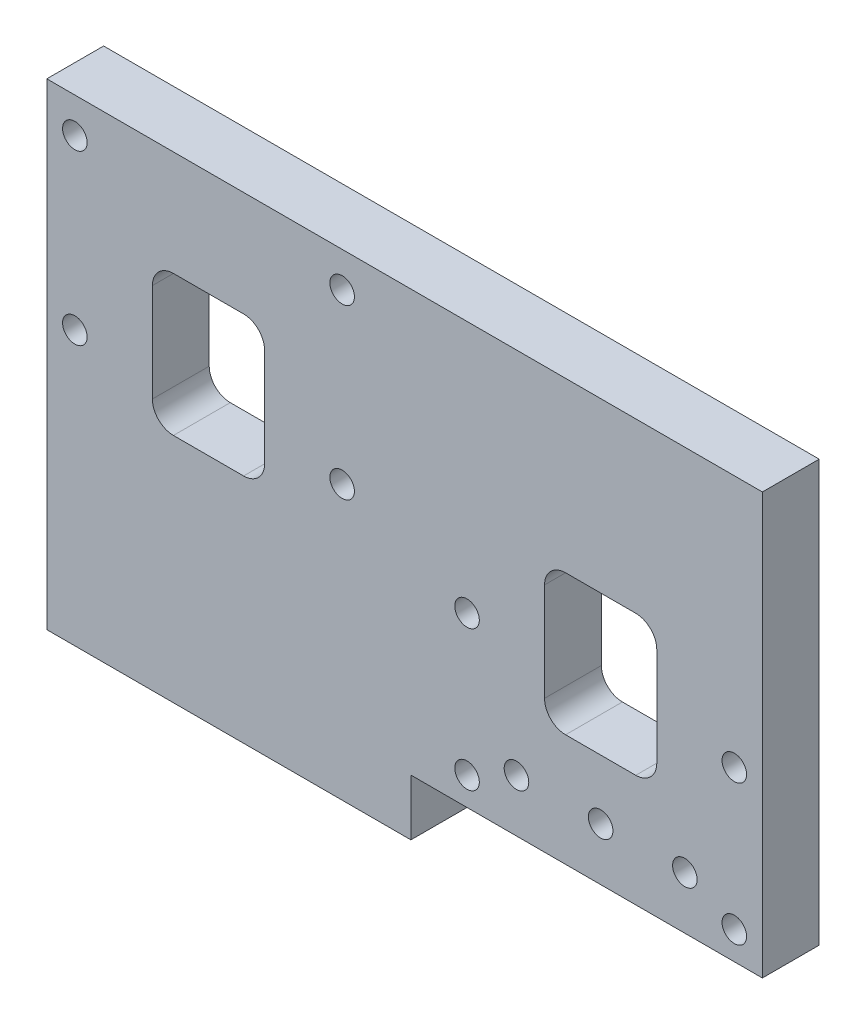
SolidWorks part; units mm, degrees
ref_plane "Plan de face" through (0, 0, 0) normal (0, 0, 1) x (1, 0, 0)
ref_plane "Plan de dessus" through (0, 0, 0) normal (0, 1, 0) x (1, 0, 0)
ref_plane "Plan de droite" through (0, 0, 0) normal (1, 0, 0) x (0, 0, -1)
sketch "Esquisse1" plane through (0, 0, 0) normal (0, 0, 1) x (1, 0, 0)
  line L1 (0, 0) -> (102, 0)
  line L2 (0, 0) -> (0, 60)
  line L3 (0, 60) -> (102, 60)
  line L4 (102, 0) -> (102, 60)
  dimension "D1" = 102
  dimension "D2" = 60
extrude "Boss.-Extru.1" add sketch "Esquisse1" along normal blind 8.1
sketch "Esquisse2" plane through (0, 0, 8.1) normal (0, 0, 1) x (1, 0, 0)
  line L0 (4, 31) -> (4, 55) construction
  line L1 (0, 60) -> (0, 0) construction
  line L2 (102, 60) -> (0, 60) construction
  line L3 (98, 4) -> (98, 24) construction
  line L4 (0, 0) -> (102, 0) construction
  line L5 (102, 0) -> (102, 60) construction
  line L6 (78.95, 0) -> (78.95, 26.94) construction
  line L7 (59.9, 4) -> (59.9, 24) construction
  line L8 (23.05, 60) -> (23.05, 33.0789) construction
  line L9 (42.1, 31) -> (42.1, 55) construction
  line L10 (78.95, 7.5) -> (66.95, 7.5) construction
  circle A0 centre (4, 55) radius 1.75
  circle A1 centre (4, 31) radius 1.75
  circle A2 centre (98, 24) radius 1.75
  circle A3 centre (98, 4) radius 1.75
  circle A4 centre (59.9, 4) radius 1.75
  circle A5 centre (59.9, 24) radius 1.75
  circle A6 centre (42.1, 31) radius 1.75
  circle A7 centre (42.1, 55) radius 1.75
  circle A8 centre (66.95, 7.5) radius 1.75
  circle A9 centre (78.95, 7.5) radius 1.75
  circle A10 centre (90.95, 7.5) radius 1.75
  dimension "D1" = 3.5
  dimension "D2" = 4
  dimension "D11" = 12
  dimension "D12" = 3.5
  dimension "D3" = 5
  dimension "D4" = 24
  dimension "D5" = 4
  dimension "D6" = 4
  dimension "D7" = 20
  dimension "D8" = 38.1
  dimension "D9" = 38.1
  dimension "D10" = 7.5
extrude "Enlèv. mat.-Extru.1" cut sketch "Esquisse2" against normal through all
sketch "Esquisse5" plane through (0, 0, 8.1) normal (0, 0, 1) x (1, 0, 0)
  line L0 (102, 0) -> (102, 60) construction
  line L1 (0, 0) -> (51.9, 0)
  line L2 (0, 0) -> (0, -8)
  line L3 (0, -8) -> (51.9, -8)
  line L4 (51.9, 0) -> (51.9, -8)
  dimension "D1" = 8
  dimension "D2" = 50.1
extrude "Boss.-Extru.2" add sketch "Esquisse5" against normal up to vertex (8.1 mm away) up to point (0, 0, 0)
sketch "Esquisse6" plane through (0, 0, 8.1) normal (0, 0, 1) x (1, 0, 0)
  line L0 (4, 55) -> (42.1, 55) construction
  line L1 (15.05, 45) -> (31.05, 45)
  line L2 (15.05, 45) -> (15.05, 25)
  line L3 (15.05, 25) -> (31.05, 25)
  line L4 (31.05, 45) -> (31.05, 25)
  line L5 (86.95, 36) -> (70.95, 36)
  line L6 (86.95, 36) -> (86.95, 16)
  line L7 (86.95, 16) -> (70.95, 16)
  line L8 (70.95, 36) -> (70.95, 16)
  line L9 (23.05, 45) -> (23.05, 55) construction
  line L10 (59.9, 24) -> (98, 24) construction
  line L11 (78.95, 16) -> (78.95, 24) construction
  line L12 (51.9, 0) -> (102, 0) construction
  point P22 (76.95, 0)
  dimension "D1" = 16
  dimension "D2" = 20
  dimension "D3" = 10
  dimension "D4" = 16
extrude "Enlèv. mat.-Extru.2" cut sketch "Esquisse6" against normal through all
fillet "Congé1" radius 3 8 edges at (15.05, 25, 4.05) (31.05, 25, 4.05) (31.05, 45, 4.05) (15.05, 45, 4.05) (86.95, 16, 4.05) (86.95, 36, 4.05) (70.95, 36, 4.05) (70.95, 16, 4.05)
